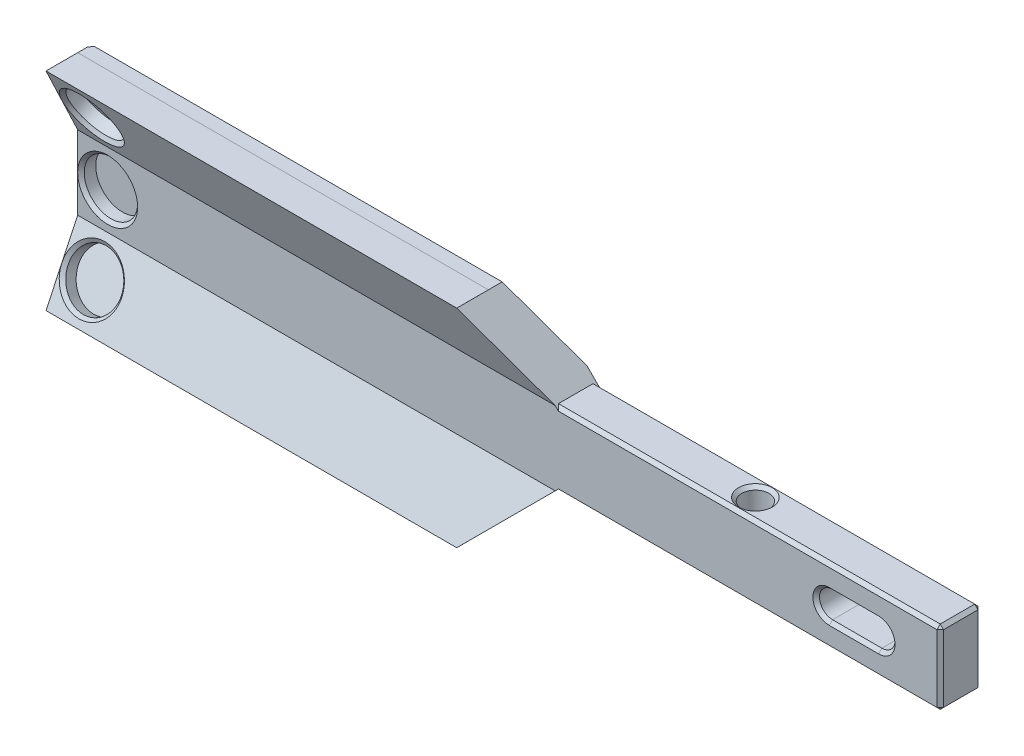
SolidWorks part; units mm, degrees
ref_plane "Front" through (0, 0, 0) normal (0, 0, 1) x (1, 0, 0)
ref_plane "Top" through (0, 0, 0) normal (0, 1, 0) x (1, 0, 0)
ref_plane "Right" through (0, 0, 0) normal (1, 0, 0) x (0, 0, -1)
sketch "Sketch1" plane through (0, 0, 0) normal (0, 0, 1) x (1, 0, 0)
  line L1 (52.5, -4.5) -> (-52.5, -4.5)
  line L2 (52.5, -4.5) -> (52.5, 4.5)
  line L3 (52.5, 4.5) -> (-52.5, 4.5)
  line L4 (-52.5, -4.5) -> (-52.5, 4.5)
  line L5 (52.5, -4.5) -> (-52.5, 4.5) construction
  line L6 (52.5, 4.5) -> (-52.5, -4.5) construction
  point P0 (0, 0)
  dimension "D1" = 9
  dimension "D2" = 105
extrude "Boss-Extrude1" add sketch "Sketch1" along normal blind 5
sketch "Sketch2" plane through (0, 4.5, 0) normal (0, 1, 0) x (1, 0, 0)
  line L0 (52.5, -5) -> (52.5, 0) construction
  line L2 (52.5, 0) -> (-52.5, 0) construction
  circle A0 centre (27.5, -2.5) radius 1.65
  dimension "D3" = 3.3
  dimension "D1" = 2.5
  dimension "D2" = 25
sketch "Sketch4" plane through (0, 0, 5) normal (0, 0, 1) x (1, 0, 0)
  line L0 (39, 0) -> (45, 0) construction
  line L1 (39, 1.6) -> (45, 1.6)
  line L2 (39, -1.6) -> (45, -1.6)
  arc A0 (39, 1.6) -> (39, -1.6) centre (39, 0) ccw
  arc A1 (45, -1.6) -> (45, 1.6) centre (45, 0) ccw
  point P2 (42, 0)
  dimension "D1" = 1.6
  dimension "D2" = 42
  dimension "D3" = 6
extrude "Cut-Extrude1" cut sketch "Sketch4" against normal blind 5
sketch "Sketch8" plane through (0, 0, 0) normal (0, 0, -1) x (-1, 0, 0)
  line L0 (52.5, 4.5) -> (52.5, -4.5) construction
  line L1 (52.5, 12.63) -> (2.5, 12.63)
  line L2 (52.5, 12.63) -> (52.5, -12.63)
  line L3 (52.5, -12.63) -> (2.5, -12.63)
  line L4 (2.5, 12.63) -> (2.5, -12.63)
  line L6 (-52.5, 4.5) -> (52.5, 4.5) construction
  dimension "D1" = 25.26
  dimension "D2" = 8.13
  dimension "D3" = 50
extrude "Boss-Extrude3" add sketch "Sketch8" against normal up to surface (5 mm away) up to face at (42, 0, 5)
sketch "Sketch9" plane through (-52.5, 0, 0) normal (-1, 0, 0) x (0, 0, 1)
  line L0 (5, 12.63) -> (5, -12.63) construction
  line L1 (5, 12.6327) -> (8.8548, 12.6327)
  line L2 (8.8548, 12.6327) -> (5, 4.5)
  line L3 (5, 4.5) -> (5, 12.6327)
  line L4 (-3.9634, 0) -> (12.9509, 0) construction
  line L5 (8.8548, -12.6327) -> (5, -4.5)
  line L6 (5, -12.6327) -> (8.8548, -12.6327)
  line L7 (5, -4.5) -> (5, -12.6327)
  circle A0 centre (25, 0) radius 20 construction
  dimension "D1" = 40
  dimension "D2" = 9
  dimension "D3" = 9
extrude "Boss-Extrude4" add sketch "Sketch9" against normal up to surface (50 mm away) up to face at (-2.5, 8.565, 2.5)
sketch "Sketch13" plane through (-52.5, 0, 0) normal (-1, 0, 0) x (0, 0, 1)
  line L0 (0, 5.625) -> (3.3203, 12.63)
  line L1 (0, 12.63) -> (0, -12.63) construction
  line L2 (5, 12.63) -> (0, 12.63) construction
  line L3 (3.3203, 12.63) -> (-2, 12.63)
  line L4 (-2, 12.63) -> (-2, -12.63)
  line L5 (-2, -12.63) -> (3.3203, -12.63)
  line L6 (5, -12.63) -> (0, -12.63) construction
  line L7 (3.3203, -12.63) -> (0, -5.625)
  line L8 (0, -5.625) -> (0, 5.625)
  line L10 (5, 4.5) -> (8.8548, 12.6327) construction
  line L11 (8.8548, -12.6327) -> (5, -4.5) construction
  point P16 (-2, -13.9962)
  dimension "D1" = 5
  dimension "D2" = 5
  dimension "D3" = 2
extrude "Cut-Extrude6" cut sketch "Sketch13" against normal through all
chamfer "Chamfer4" distance 8.13 2 edges at (-2.5, 4.5, 2.5) (-2.5, -4.5, 2.5)
sketch "Sketch10" plane through (-52.5, 0, 0) normal (-1, 0, 0) x (0, 0, 1)
  line L0 (5, 4.5) -> (5, -4.5) construction
  line L1 (5, 4.5) -> (8.8548, 12.6327) construction
  line L2 (8.8548, -12.6327) -> (5, -4.5) construction
  circle A0 centre (25, 0) radius 20
sketch "Sketch11" plane through (0, 0, 5) normal (0, 0, 1) x (1, 0, 0)
  line L2 (-52.5, 4.5) -> (-52.5, -4.5) construction
  circle A0 centre (-48.85, 0) radius 3.25
  dimension "D1" = 6.5
  dimension "D2" = 3.65
extrude "Cut-Extrude3" cut sketch "Sketch11" against normal blind 1.8
sketch "Sketch12" plane through (0, -1.1096, 2.341) normal (0, -0.4283, 0.9036) x (1, 0, 0)
  line L1 (-2.5, 15.2079) -> (-52.5, 15.2079) construction
  line L2 (-52.5, 30.7079) -> (-52.5, -9.2921) construction
  circle A0 centre (-48.85, 10.7079) radius 3.25
  dimension "D1" = 6.5
  dimension "D2" = 4.5
  dimension "D3" = 3.65
extrude "Cut-Extrude4" cut sketch "Sketch12" against normal blind 1.8
mirror "Mirror2" about plane through (0, 0, 0) normal (0, 1, 0) of "Cut-Extrude4"
chamfer "Chamfer2" distance 0.4 angle 45 3 edges at (-45.6, 0, 5) (-48.85, -5.6295, 5.5354) (-48.85, 5.6295, 5.5354)
ref_plane "Plane1" through (-48.5, 0, 0) normal (-1, 0, 0) x (0, 0, 1)
extrude "Cut-Extrude5" cut sketch "Sketch2" against normal blind 10
chamfer "Chamfer5" distance 0.4 angle 45 18 edges at (25.85, -4.5, 2.5) (25.85, 4.5, 2.5) (52.5, 4.5, 2.5) (29.065, 4.5, 5) (52.5, 0, 5) (29.065, -4.5, 5) (52.5, -4.5, 2.5) (29.065, 4.5, 0) (29.065, -4.5, 0) (52.5, 0, 0) (42, -1.6, 0) (46.6, 0, 0) (37.4, 0, 0) (42, 1.6, 0) (42, 1.6, 5) (37.4, 0, 5) (46.6, 0, 5) (42, -1.6, 5)
chamfer "Chamfer6" distance 0.4 angle 45 3 edges at (-52.5, 9.1275, 1.6602) (-52.5, -9.1275, 1.6602) (-52.5, 0, 0)
